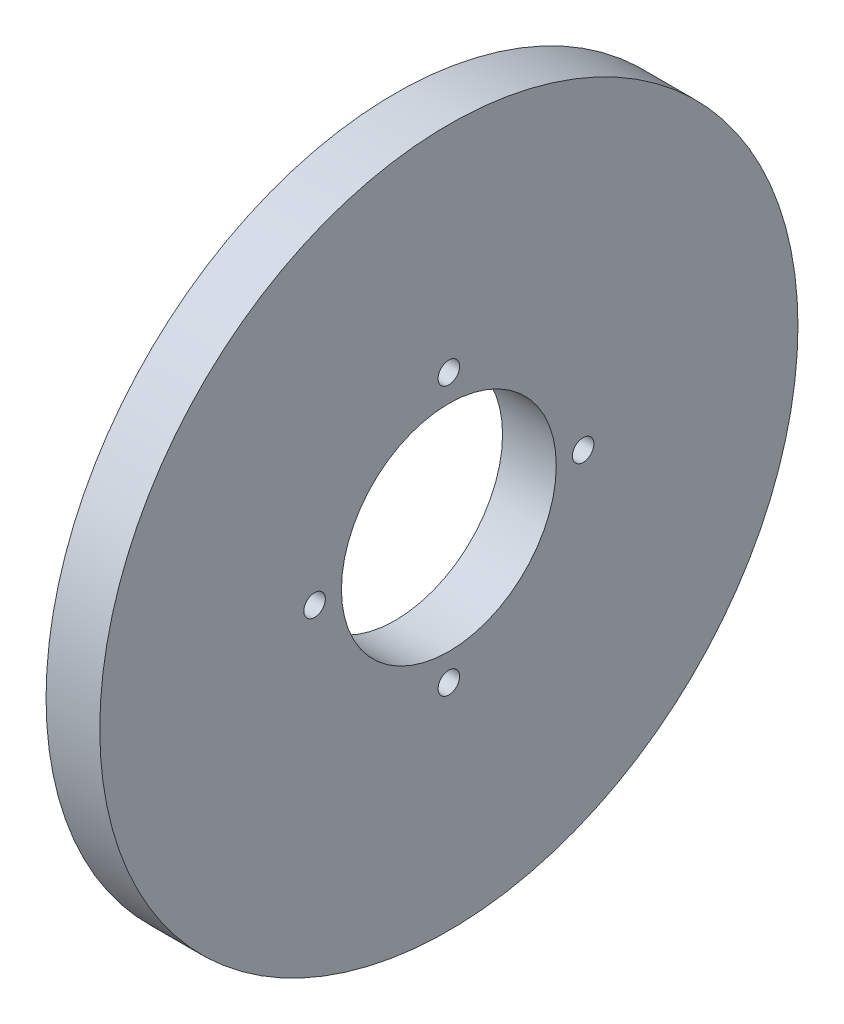
SolidWorks part; units mm, degrees
material "2024-T4"
ref_plane "Front Plane" through (0, 0, 0) normal (0, 0, 1) x (1, 0, 0)
ref_plane "Top Plane" through (0, 0, 0) normal (0, 1, 0) x (1, 0, 0)
ref_plane "Right Plane" through (0, 0, 0) normal (1, 0, 0) x (0, 0, -1)
sketch "Sketch1" plane through (0, 0, 0) normal (1, 0, 0) x (0, 0, -1)
  circle A0 centre (0, 0) radius 20
  circle A1 centre (0, 0) radius 65
  dimension "D1" = 130
  dimension "D2" = 40
extrude "Boss-Extrude1" add sketch "Sketch1" along normal mid plane 10
sketch "Sketch2" plane through (5, 0, 0) normal (1, 0, 0) x (0, 0, -1)
  circle A0 centre (0, 0) radius 25 construction
  circle A1 centre (0, 25) radius 2
  circle A2 centre (25, 0) radius 2
  circle A3 centre (0, -25) radius 2
  circle A4 centre (-25, 0) radius 2
  point P14 (0, 0)
  dimension "D1" = 50
  dimension "D2" = 4
  dimension "D4" = 25
  dimension "D5" = 25
  dimension "D3" = 4
extrude "Cut-Extrude1" cut sketch "Sketch2" against normal through all
